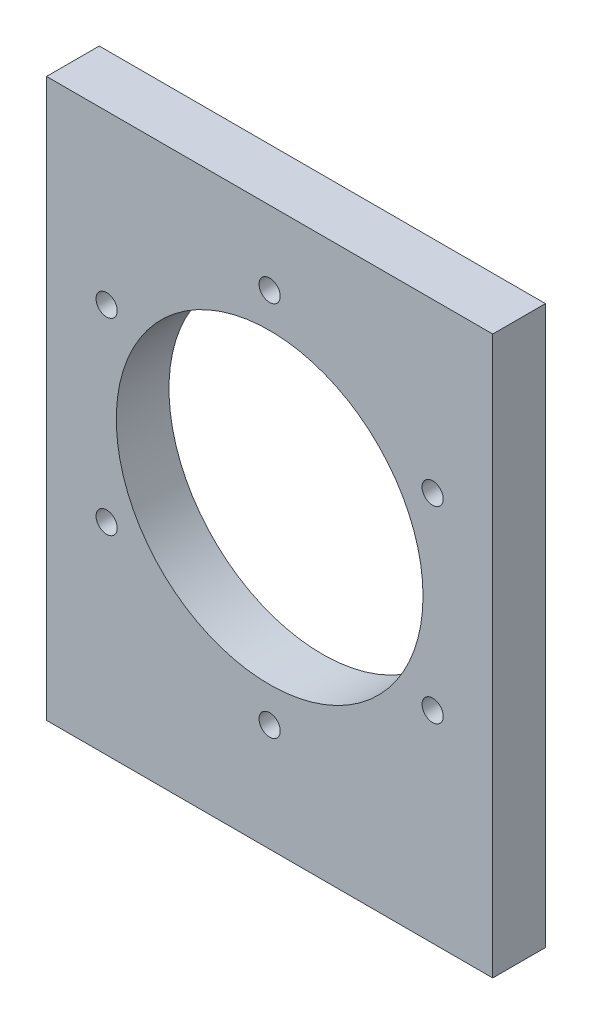
SolidWorks part; units mm, degrees
ref_plane "Front Plane" through (0, 0, 0) normal (0, 0, 1) x (1, 0, 0)
ref_plane "Top Plane" through (0, 0, 0) normal (0, 1, 0) x (1, 0, 0)
ref_plane "Right Plane" through (0, 0, 0) normal (1, 0, 0) x (0, 0, -1)
sketch "Sketch1" plane through (0, 0, 0) normal (0, 0, 1) x (1, 0, 0)
  line L1 (-50.8, 127) -> (50.8, 127)
  line L2 (-50.8, 127) -> (-50.8, 0)
  line L3 (-50.8, 0) -> (50.8, 0)
  line L4 (50.8, 127) -> (50.8, 0)
  circle A0 centre (0, 67.375) radius 34.925
  circle A1 centre (-37.12, 45.9437) radius 2.413
  circle A2 centre (37.12, 45.9437) radius 2.413
  circle A3 centre (0, 24.5125) radius 2.413
  circle A4 centre (-37.12, 88.8062) radius 2.413
  circle A5 centre (37.12, 88.8062) radius 2.413
  circle A6 centre (0, 110.2375) radius 2.413
  dimension "D1" = 127
  dimension "D3" = 69.85
  dimension "D4" = 42.8625
  dimension "D6" = 4.826
  dimension "D7" = 4.826
  dimension "D8" = 4.826
  dimension "D9" = 4.826
  dimension "D10" = 4.826
  dimension "D11" = 4.826
  dimension "D2" = 101.6
  dimension "D5" = 67.375
extrude "Boss-Extrude1" add sketch "Sketch1" along normal blind 12
